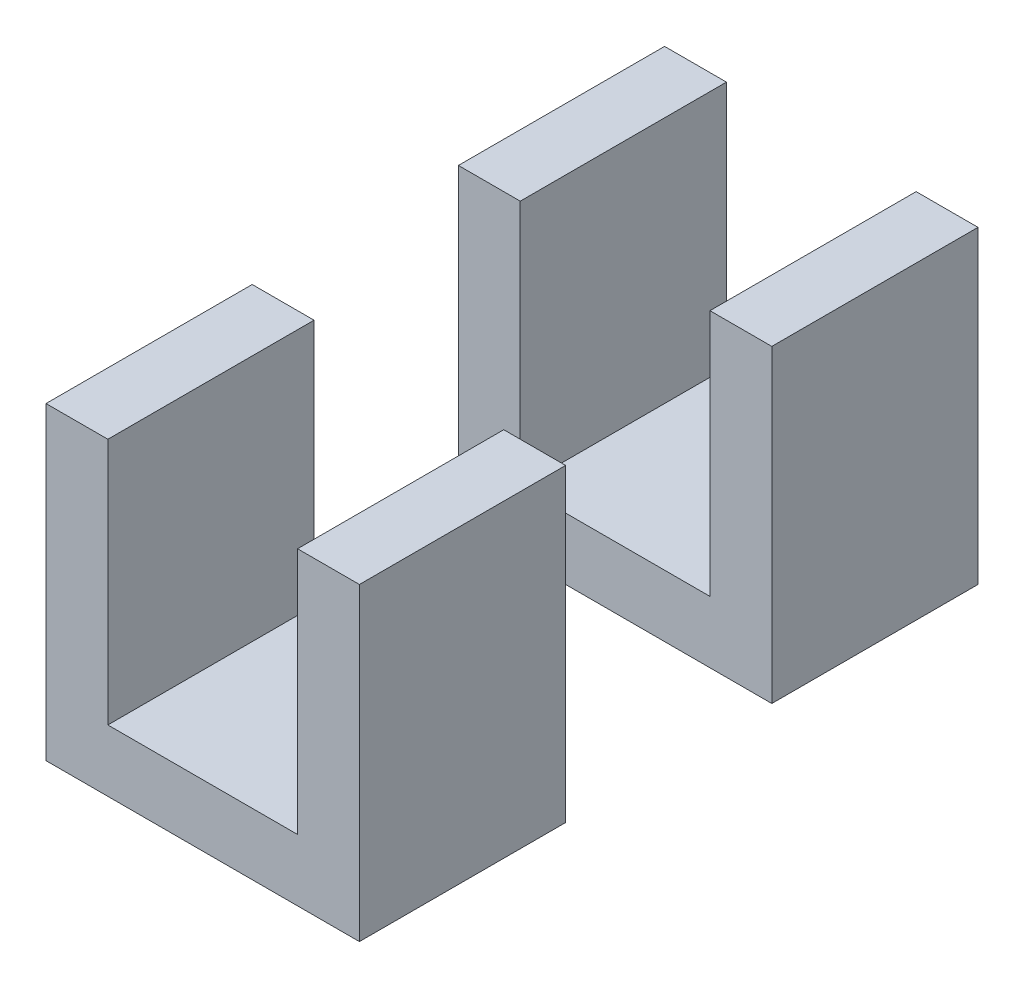
SolidWorks part; units mm, degrees
ref_plane "Front Plane" through (0, 0, 0) normal (0, 0, 1) x (1, 0, 0)
ref_plane "Top Plane" through (0, 0, 0) normal (0, 1, 0) x (1, 0, 0)
ref_plane "Right Plane" through (0, 0, 0) normal (1, 0, 0) x (0, 0, -1)
ref_axis "Axis1" through (0, 0, 72.3583) along (0, 0, -1)
sketch "Sketch1" plane through (0, 0, 0) normal (0, 0, 1) x (1, 0, 0)
  line L0 (-4.6, 15) -> (-4.6, 3)
  line L1 (-4.6, 3) -> (4.6, 3)
  line L2 (4.6, 3) -> (4.6, 15)
  line L3 (4.6, 15) -> (7.6, 15)
  line L4 (7.6, 15) -> (7.6, 0)
  line L5 (7.6, 0) -> (-7.6, 0)
  line L6 (-7.6, 0) -> (-7.6, 15)
  line L7 (-7.6, 15) -> (-4.6, 15)
  point P7 (0, 3)
  point P10 (0, 0)
  point P11 (4.3446, 3)
  point P12 (-3.0386, 15)
  point P13 (3.9121, 0)
  point P14 (4.0048, 0)
  point P15 (-5, -2.7649)
  point P16 (0.201, 4.8069)
  dimension "D1" = 9.2
  dimension "D2" = 12
  dimension "D3" = 3
  dimension "D4" = 3
extrude "Boss-Extrude1" add sketch "Sketch1" along normal blind 10
pattern_linear "LPattern3" count 2 spacing 20 along (0, 0, 1) of "Boss-Extrude1"
